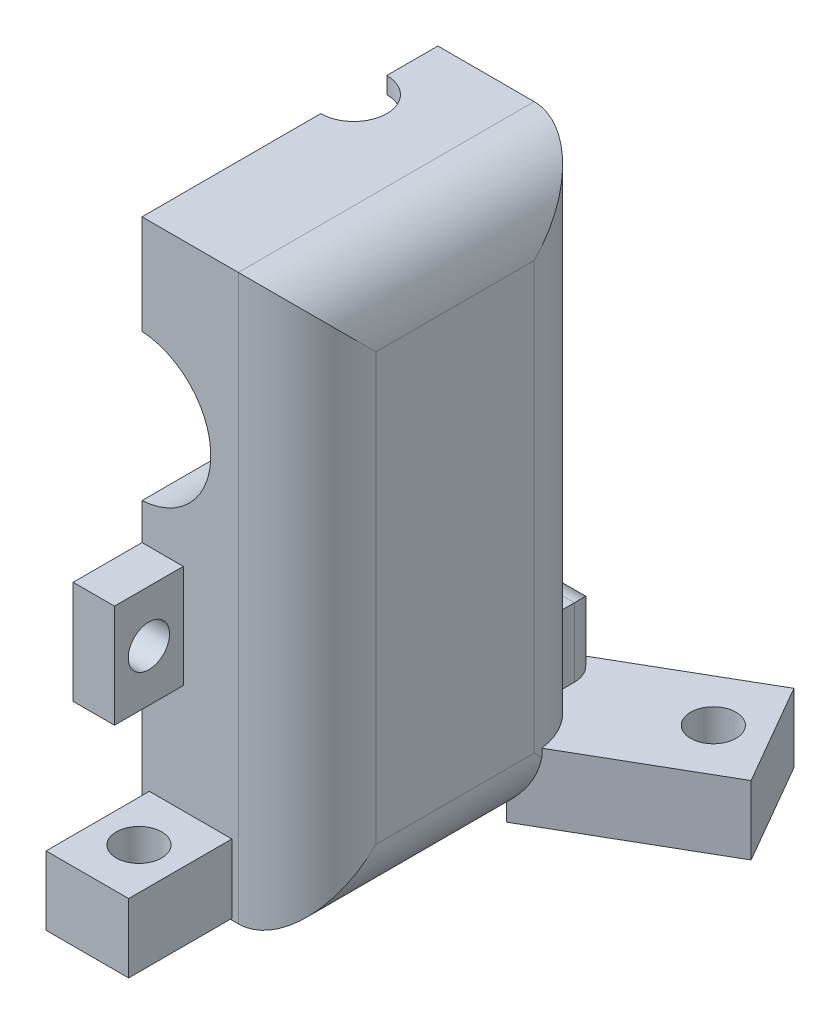
SolidWorks part; units mm, degrees
material "PET"
ref_plane "Alzado" through (0, 0, 0) normal (0, 0, 1) x (1, 0, 0)
ref_plane "Planta" through (0, 0, 0) normal (0, 1, 0) x (1, 0, 0)
ref_plane "Vista lateral" through (0, 0, 0) normal (1, 0, 0) x (0, 0, -1)
sketch "Croquis2" plane through (0, 0, 0) normal (1, 0, 0) x (0, 0, -1)
  line L1 (21.5, -41) -> (-21.5, -41)
  line L2 (21.5, -41) -> (21.5, 41)
  line L3 (21.5, 41) -> (-21.5, 41)
  line L4 (-21.5, -41) -> (-21.5, 41)
  line L5 (21.5, -41) -> (-21.5, 41) construction
  line L6 (21.5, 41) -> (-21.5, -41) construction
  point P0 (0, 0)
  dimension "D1" = 43
  dimension "D2" = 82
extrude "Saliente-Extruir1" add sketch "Croquis2" along normal blind 24
sketch "Croquis3" plane through (0, 0, 0) normal (-1, 0, 0) x (0, 0, 1)
  line L0 (21.5, -41) -> (-21.5, -41) construction
  line L1 (-18.8495, 38.582) -> (5.3783, 38.582)
  line L2 (-18.8495, 38.582) -> (-18.8495, -41)
  line L3 (-18.8495, -41) -> (5.3783, -41)
  line L4 (5.3783, 38.582) -> (5.3783, -41)
extrude "Cortar-Extruir1" cut sketch "Croquis3" against normal blind 16
sketch "Croquis4" plane through (0, 0, 0) normal (-1, 0, 0) x (0, 0, 1)
  line L0 (5.3783, 38.582) -> (5.3783, 26.582)
  line L1 (5.3783, -41) -> (5.3783, 38.582) construction
  line L2 (5.3783, 26.582) -> (21.5, 26.582)
  line L3 (21.5, 41) -> (21.5, -41) construction
  line L4 (21.5, 26.582) -> (21.5, 5.2885)
  line L5 (21.5, 5.2885) -> (5.3783, 5.2885)
  line L6 (5.3783, -41) -> (5.3783, 38.582) construction
  line L7 (5.3783, 5.2885) -> (5.3783, 26.582)
  dimension "D1" = 21.2935
  dimension "D2" = 12
extrude "Cortar-Extruir2" cut sketch "Croquis4" against normal blind 10 contours L2 L4 L5 L7
sketch "Croquis5" plane through (0, 41, 0) normal (0, 1, 0) x (1, 0, 0)
  line L0 (0, 21.5) -> (0, -21.5) construction
  line L1 (0, 14.078) -> (0, 4.478)
  arc A0 (0, 14.078) -> (0, 4.478) centre (0, 9.278) cw
  dimension "D1" = 4.8
extrude "Cortar-Extruir4" cut sketch "Croquis5" against normal through all
mirror "Simetría2" [suppressed] of bodies 105
delete or keep bodies "Sólido-Eliminar/Conservar 1" [suppressed] type delete bodies bodies 105
fillet "Redondeo1" radius 10 4 edges at (24, 0, 21.5) (24, -41, 0) (24, 0, -21.5) (24, 41, 0) type face fillet first side face at (8.8, 41, -3.0927) first side face at (12, 0, -21.5) first side face at (8.5, 7.9676, 21.5) first side face at (10, -41, -3.3678) second side face at (24, 0, 0)
fillet "Redondeo5" [suppressed] radius 10
sketch "Croquis6" [suppressed] plane through (0, 0, 21.5) normal (0, 0, 1) x (1, 0, 0)
  line L8 (0, 41) -> (-14, 41)
  line L9 (-14, 41) -> (-14, -41)
  line L10 (-14, -41) -> (0, -41)
  line L11 (0, -41) -> (0, 9.4394)
  line L12 (0, 9.4394) -> (-10, 9.4394)
  line L13 (-10, 9.4394) -> (-10, 30.7329)
  line L14 (-10, 30.7329) -> (0, 30.7329)
  line L15 (0, 30.7329) -> (0, 41)
  line L16 (0, 41) -> (-14, 41)
  line L17 (-14, 41) -> (-14, -41)
  line L18 (-14, -41) -> (0, -41)
  line L19 (0, -41) -> (0, 9.4394)
  line L23 (0, 30.7329) -> (0, 41)
  arc A0 (0, 30.7329) -> (0, 9.4394) centre (0.6677, 20.0862) ccw
  dimension "D1" = 0
extrude "Saliente-Extruir2" [suppressed] add sketch "Croquis6" against normal blind 19 contours A0 L19 L18 L17 L16 L23
sketch "Croquis7" plane through (0, 0, 21.5) normal (0, 0, 1) x (1, 0, 0)
  line L8 (0, -41) -> (14, -41)
  line L9 (14, -41) -> (14, 41)
  line L10 (14, 41) -> (0, 41)
  line L11 (0, 41) -> (0, 26.582)
  line L12 (0, 26.582) -> (10, 26.582)
  line L13 (10, 26.582) -> (10, 5.2885)
  line L14 (10, 5.2885) -> (0, 5.2885)
  line L15 (0, 5.2885) -> (0, -41)
  line L16 (0, -41) -> (14, -41)
  line L17 (14, -41) -> (14, 41)
  line L18 (14, 41) -> (0, 41)
  line L19 (0, 41) -> (0, 26.582)
  line L23 (0, 5.2885) -> (0, -41)
  arc A0 (0, 5.2885) -> (0, 26.582) centre (-0.6677, 15.9353) ccw
  dimension "D1" = 0
extrude "Saliente-Extruir3" add sketch "Croquis7" against normal blind 16
sketch "Croquis8" plane through (0, 0, -21.5) normal (0, 0, -1) x (-1, 0, 0)
  line L0 (0, 41) -> (0, 21)
  line L1 (0, -41) -> (0, 41) construction
  line L2 (0, -41) -> (0, -21)
  line L3 (0, 21) -> (-4.9095, 21)
  line L4 (0, 21) -> (0, 6)
  line L5 (0, 6) -> (-4.9095, 6)
  line L6 (-4.9095, 21) -> (-4.9095, 6)
  line L8 (0, -21) -> (-4.9095, -21)
  line L9 (0, -21) -> (0, -6)
  line L10 (0, -6) -> (-4.9095, -6)
  line L11 (-4.9095, -21) -> (-4.9095, -6)
  line M8 (0, -41) -> (0, 41)
  dimension "D1" = 20
  dimension "D2" = 15
  dimension "D3" = 20
  dimension "D4" = 15
extrude "Saliente-Extruir4" add sketch "Croquis8" along normal blind 10 contours L3 L6 L5 M8 | L11 L8 L10 M8 region at (2.4547, 13.5, -21.5) region at (2.4547, -13.5, -21.5)
sketch "Croquis9" plane through (4.9095, 0, 0) normal (1, 0, 0) x (0, 0, -1)
  line L0 (31.5, 21) -> (31.5, 6) construction
  line L1 (31.5, -21) -> (31.5, -6) construction
  circle A0 centre (26.5, 13.5) radius 3
  circle A1 centre (26.5, -13.5) radius 3
  point P7 (31.5, 13.5)
  point P11 (31.5, -13.5)
  dimension "D1" = 6
  dimension "D2" = 6
extrude "Cortar-Extruir5" cut sketch "Croquis9" against normal up to vertex (4.9095 mm away) up to point (0, 6, -21.5)
sketch "Croquis10" plane through (0, -41, 0) normal (0, -1, 0) x (-1, 0, 0)
  line L2 (0, -21.5) -> (0, -5.3783) construction
  circle A0 centre (0, -16.3324) radius 3.2
  line M2 (0, -21.5) -> (0, -5.3783)
  dimension "D1" = 6.4
extrude "Saliente-Extruir5" add sketch "Croquis10" along normal blind 9.5 contours A0 M2 region at (1.3581, -41, 16.3324)
sketch "Croquis12" plane through (0, 0, 0) normal (-1, 0, 0) x (0, 0, 1)
  line L0 (5.3783, -40.798) -> (5.3783, 38.582) construction
  line L1 (5.3783, -20) -> (13.8767, -20)
  line L2 (5.3783, -20) -> (5.3783, -41)
  line L3 (5.3783, -41) -> (13.8767, -41)
  line L4 (13.8767, -20) -> (13.8767, -41)
  line L5 (13.1324, -41) -> (5.3783, -41) construction
  line L6 (-18.8495, 38.582) -> (-18.8495, -41) construction
  line L7 (-18.8495, -21) -> (-27.3436, -21)
  line L8 (-18.8495, -21) -> (-18.8495, -41)
  line L9 (-18.8495, -41) -> (-27.3436, -41)
  line L10 (-27.3436, -21) -> (-27.3436, -41)
  line M11 (5.3783, 5.2885) -> (5.3783, -41)
  line M12 (5.3783, -41) -> (13.1324, -41)
  dimension "D1" = 21
  dimension "D2" = 8.4984
  dimension "D3" = 20
  dimension "D4" = 8.4942
extrude "Saliente-Extruir6" add sketch "Croquis12" against normal blind 18 contours L7 L10 L9 L8 region at (0, -31, -23.0965)
extrude "Cortar-Extruir6" cut sketch "Croquis12<3>" against normal blind 15 contours L4 L1 M11 M12 region at (0, -30.5, 9.6275)
sketch "Croquis12<3>" plane through (0, 0, 0) normal (-1, 0, 0) x (0, 0, 1) same geometry as "Croquis12"
sketch "Croquis13" plane through (0, 0, 0) normal (-1, 0, 0) x (0, 0, 1)
  line L1 (-18.8495, -41) -> (-23.7971, -41)
  line L2 (-18.8495, -41) -> (-18.8495, -23.6817)
  line L3 (-18.8495, -23.6817) -> (-23.7971, -23.6817)
  line L4 (-23.7971, -41) -> (-23.7971, -23.6817)
extrude "Cortar-Extruir8" cut sketch "Croquis13" against normal blind 15
fillet "Redondeo6" radius 4 3 edges at (11.4547, -21, -27.3436) (9, -41, -27.3436) (18, -31, -27.3436) tangent propagation no
sketch "Croquis14" plane through (0, 0, 21.5) normal (0, 0, 1) x (1, 0, 0)
  line L1 (1.0599, -30.7785) -> (13.0599, -30.7785)
  line L2 (1.0599, -30.7785) -> (1.0599, -40.7785)
  line L3 (1.0599, -40.7785) -> (13.0599, -40.7785)
  line L4 (13.0599, -30.7785) -> (13.0599, -40.7785)
  line L5 (1.0599, -30.7785) -> (13.0599, -40.7785) construction
  line L6 (1.0599, -40.7785) -> (13.0599, -30.7785) construction
  point P0 (7.0599, -35.7785)
  dimension "D1" = 12
  dimension "D2" = 10
extrude "Saliente-Extruir7" add sketch "Croquis14" along normal blind 15
sketch "Croquis16" plane through (0, -30.7785, 0) normal (0, 1, 0) x (1, 0, 0)
  line L0 (7.0599, -21.5) -> (7.0599, -36.5) construction
  line L1 (13.0599, -21.5) -> (1.0599, -21.5) construction
  line L2 (13.0599, -36.5) -> (1.0599, -36.5) construction
  line L3 (1.0599, -29) -> (13.0599, -29) construction
  line L4 (1.0599, -36.5) -> (1.0599, -21.5) construction
  line L5 (13.0599, -36.5) -> (13.0599, -21.5) construction
  circle A0 centre (7.0599, -29) radius 3.3
  circle A1 centre (33.5168, 28.0185) radius 3.3
  dimension "D1" = 6.6
extrude "Cortar-Extruir9" cut sketch "Croquis16" against normal through all
sketch "Croquis19" plane through (0, -41, 0) normal (0, 1, 0) x (1, 0, 0)
  line L0 (43.2211, 23.8063) -> (20.7045, 10.8063)
  line L1 (43.2211, 23.8063) -> (34.7211, 38.5288)
  line L2 (34.7211, 38.5288) -> (43.2211, 23.8063) construction
  line L3 (34.7211, 38.5288) -> (12.2045, 25.5288)
  line L4 (12.2045, 25.5288) -> (20.7045, 10.8063)
  dimension "D1" = 26
extrude "Saliente-Extruir8" add sketch "Croquis19" along normal blind 10
sketch "Croquis21" plane through (0, -31, 0) normal (0, 1, 0) x (1, 0, 0)
  circle A0 centre (33.5168, 28.0185) radius 3.3
extrude "Cortar-Extruir10" cut sketch "Croquis21" against normal through all
sketch "Croquis22" plane through (0, 0, 21.5) normal (0, 0, 1) x (1, 0, 0)
  line L1 (0, 0) -> (6, 0)
  line L2 (0, 0) -> (0, -15)
  line L3 (0, -15) -> (6, -15)
  line L4 (6, 0) -> (6, -15)
  dimension "D1" = 6
  dimension "D2" = 15
extrude "Saliente-Extruir9" add sketch "Croquis22" along normal blind 10
sketch "Croquis23" plane through (6, 0, 0) normal (1, 0, 0) x (0, 0, -1)
  circle A0 centre (-26.5, -7.5) radius 3
  dimension "D1" = 6
extrude "Cortar-Extruir11" cut sketch "Croquis23" against normal blind 10
